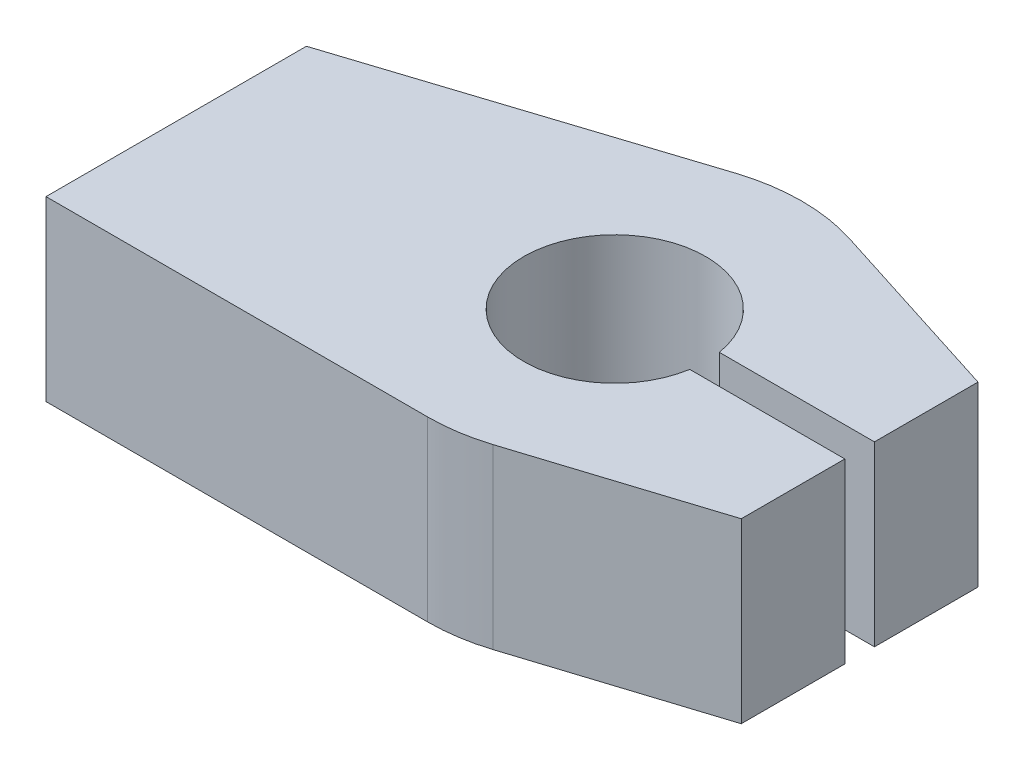
SolidWorks part; units mm, degrees
ref_plane "Front Plane" through (0, 0, 0) normal (0, 0, 1) x (1, 0, 0)
ref_plane "Top Plane" through (0, 0, 0) normal (0, 1, 0) x (1, 0, 0)
ref_plane "Right Plane" through (0, 0, 0) normal (1, 0, 0) x (0, 0, -1)
sketch "Sketch1" plane through (0, 0, 0) normal (0, 1, 0) x (1, 0, 0)
  line L0 (-12.9, -4.8198) -> (-7.1, 0.9802) construction
  line L1 (-12.9, 0.9802) -> (-7.1, 0.9802)
  line L2 (-12.9, 0.9802) -> (-12.9, -4.8198)
  line L3 (-12.9, -4.8198) -> (-7.1, -4.8198)
  line L4 (-7.1, 0.9802) -> (-7.1, -4.8198)
  line L5 (-12.9, 0.9802) -> (-7.1, -4.8198) construction
  line L6 (8.275, 4) -> (1.9154, 6.0226)
  line L7 (0, 0.5) -> (8.275, 0.5)
  line L8 (0, 0.5) -> (0, -0.5)
  line L9 (0, -0.5) -> (8.275, -0.5)
  line L10 (8.275, 0.5) -> (8.275, -0.5)
  line L11 (8.275, 4) -> (3.075, 4)
  line L12 (8.275, 4) -> (8.275, -4)
  line L13 (8.275, -4) -> (3.075, -4)
  line L14 (3.075, 4) -> (3.075, -4)
  line L15 (8.275, -4) -> (1.9154, -6.0226)
  line L16 (0, -6.3198) -> (-12.9, -6.3198)
  line L17 (-12.9, -6.3198) -> (-12.9, -4.8198)
  line L18 (-12.9, 0.9802) -> (-12.9, 2.4802)
  line L19 (-12.9, 2.4802) -> (-1.9397, 6.0148)
  circle A0 centre (0, 0) radius 3.075
  circle A1 centre (0, 0) radius 6.3198
  point P9 (-10, -1.9198)
  point P14 (0, 0)
  point P15 (3.075, 0)
  dimension "D1" = 6.15
  dimension "D3" = 5.8
  dimension "D4" = 10
  dimension "D5" = 1.9198
  dimension "D6" = 1
  dimension "D7" = 8.275
  dimension "D8" = 8
  dimension "D9" = 5.2
  dimension "D2" = 1.5
extrude "Boss-Extrude1" add sketch "Sketch1" along normal blind 6 contours A1 L19 L18 L1 L4 L3 L17 L16 | L4 L1 L2 L3 | A1 L13 L14 L9 A0 L7 L11 | L7 A1 L11 L14 | L13 A1 L9 L14 | A1 L13 L12 L9 | A1 L15 L13 | A1 L11 L6 | A1 L7 L12 L11 region at (-12.7215, 0, -1.7302) region at (-10, 0, 1.9198) region at (-0.0124, 0, -6.1509) region at (5.3814, 0, -4.5784) region at (5.3814, 0, 4.5784) region at (7.006, 0, -2.4125) region at (4.4702, 0, -2.1029) region at (7.006, 0, 2.4125) region at (4.4702, 0, 2.1029)
